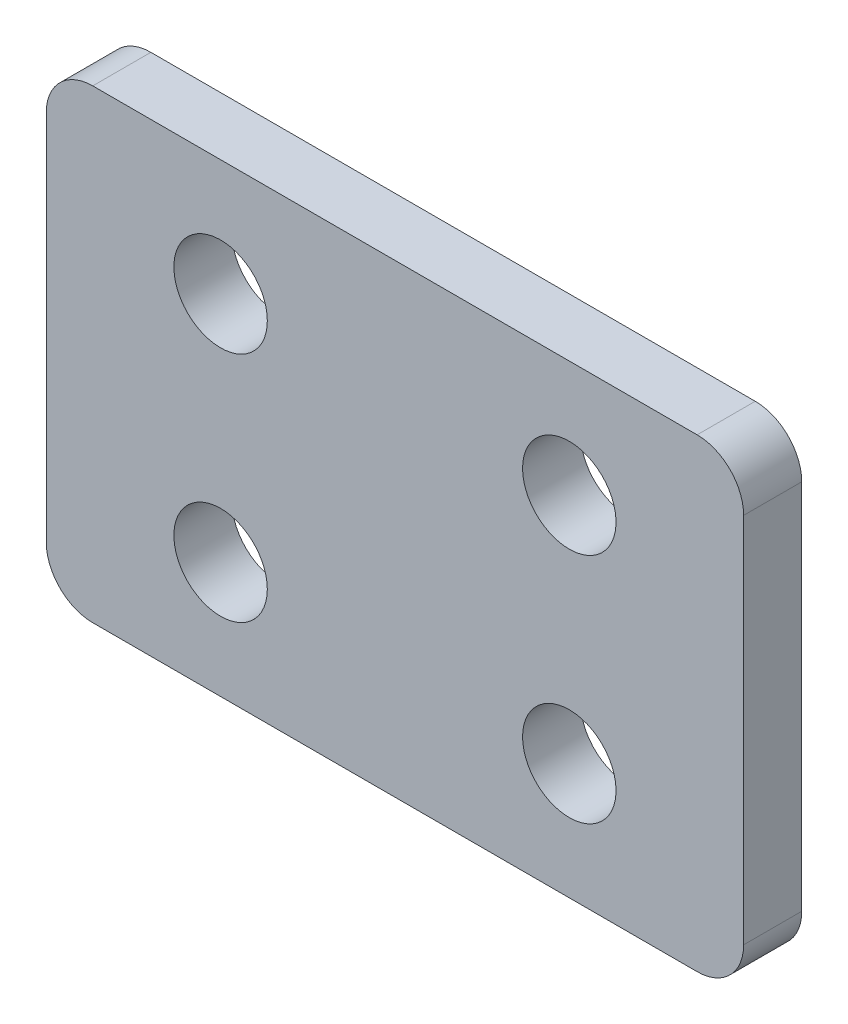
SolidWorks part; units mm, degrees
material "6061-T6 (SS)"
ref_plane "Front Plane" through (0, 0, 0) normal (0, 0, 1) x (1, 0, 0)
ref_plane "Top Plane" through (0, 0, 0) normal (0, 1, 0) x (1, 0, 0)
ref_plane "Right Plane" through (0, 0, 0) normal (1, 0, 0) x (0, 0, -1)
sketch "Sketch1" plane through (0, 0, 0) normal (0, 0, 1) x (1, 0, 0)
  line L0 (-9.525, -6.35) -> (-9.525, 6.35) construction
  line L5 (-19.05, -12.7) -> (19.05, -12.7)
  line L6 (-19.05, -12.7) -> (-19.05, 12.7)
  line L11 (-19.05, 12.7) -> (19.05, 12.7)
  line L15 (19.05, -12.7) -> (19.05, 12.7)
  line L16 (-19.05, -12.7) -> (19.05, 12.7) construction
  line L17 (-19.05, 12.7) -> (19.05, -12.7) construction
  line L18 (0, 12.7) -> (0, -12.7) construction
  circle A13 centre (-9.525, -6.35) radius 2.5527
  circle A14 centre (-9.525, 6.35) radius 2.5527
  circle A17 centre (9.525, -6.35) radius 2.5527
  circle A18 centre (9.525, 6.35) radius 2.5527
  point P0 (0, 0)
  dimension "D2" = 12.7
  dimension "D4" = 19.05
  dimension "D5" = 5.1054
  dimension "D3" = 6.35
  dimension "D7" = 25.4
  dimension "D1" = 2
  dimension "D6" = 38.1
extrude "Boss-Extrude1" add sketch "Sketch1" along normal blind 3.175
fillet "Fillet1" radius 2.54 4 edges at (-19.05, 12.7, 1.5875) (-19.05, -12.7, 1.5875) (19.05, -12.7, 1.5875) (19.05, 12.7, 1.5875)
